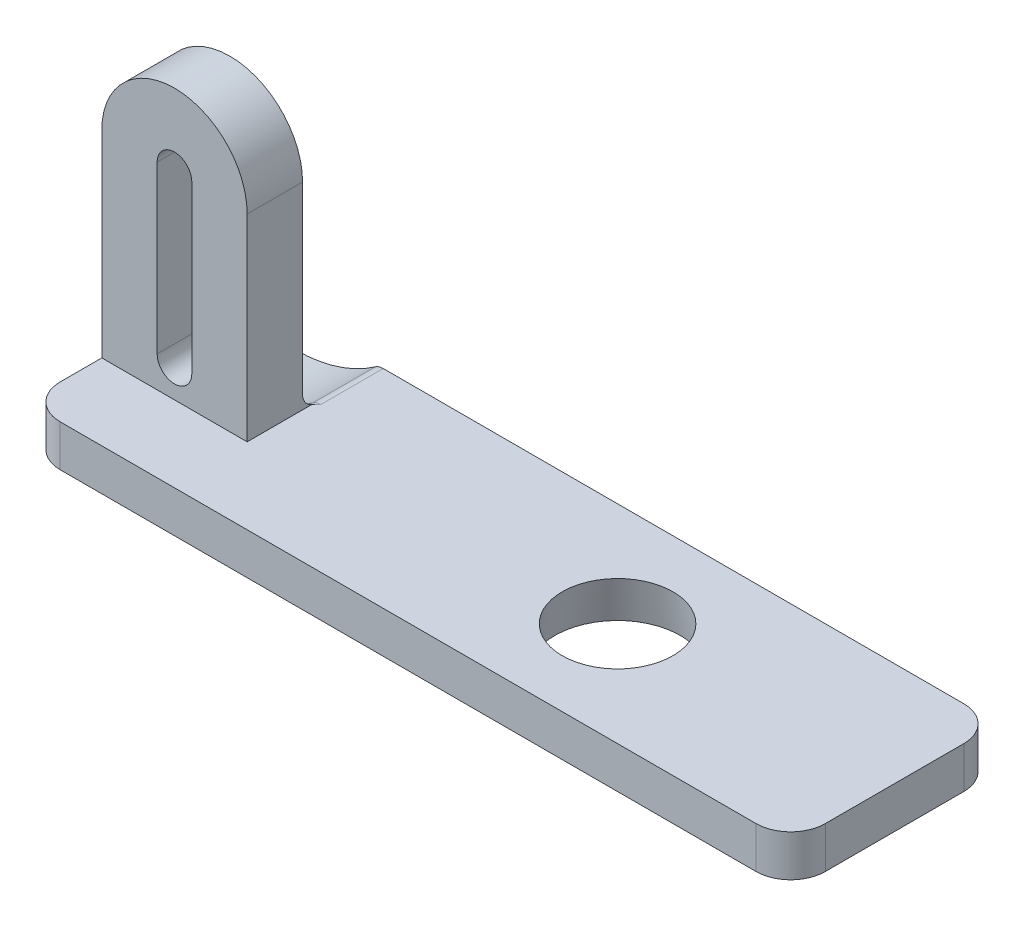
SolidWorks part; units mm, degrees
ref_plane "Front Plane" through (0, 0, 0) normal (0, 0, 1) x (1, 0, 0)
ref_plane "Top Plane" through (0, 0, 0) normal (0, 1, 0) x (1, 0, 0)
ref_plane "Right Plane" through (0, 0, 0) normal (1, 0, 0) x (0, 0, -1)
sketch "Sketch1" plane through (0, 0, 0) normal (0, 0, 1) x (1, 0, 0)
  line L0 (0, 12) -> (0, 0) construction
  line L1 (1.25, 12) -> (1.25, 0)
  line L2 (-1.25, 12) -> (-1.25, 0)
  line L3 (-5.25, 12) -> (-5.25, -5.25)
  line L4 (-5.25, -5.25) -> (50, -5.25)
  line L5 (5.25, 12) -> (5.25, -2.25)
  line L6 (5.25, -2.25) -> (50, -2.25)
  line L7 (50, -2.25) -> (50, -5.25)
  arc A0 (1.25, 12) -> (-1.25, 12) centre (0, 12) ccw
  arc A1 (-1.25, 0) -> (1.25, 0) centre (0, 0) ccw
  arc A2 (-5.25, 12) -> (5.25, 12) centre (0, 12) cw
  point P2 (0, 6)
  point P12 (0, -1.25)
  dimension "D3" = 4
  dimension "D1" = 12
  dimension "D2" = 2.5
  dimension "D4" = 4
  dimension "D5" = 50
  dimension "D6" = 3
extrude "Boss-Extrude1" add sketch "Sketch1" along normal mid plane 15
sketch "Sketch2" plane through (0, 0, 7.5) normal (0, 0, 1) x (1, 0, 0)
  line L0 (-5.25, 12) -> (-5.25, -5.25) construction
  line L1 (5.25, -2.25) -> (5.25, 12) construction
  line L2 (-5.25, 12) -> (-5.25, -2.25)
  line L3 (5.25, -2.25) -> (5.25, 12)
  line L4 (5.25, -2.25) -> (-5.25, -2.25)
  arc A0 (5.25, 12) -> (-5.25, 12) centre (0, 12) ccw construction
  arc A1 (5.25, 12) -> (-5.25, 12) centre (0, 12) ccw
extrude "Cut-Extrude1" cut sketch "Sketch2" against normal offset from surface (5.5 mm away) 2 up to plane "Front Plane"
extrude "Cut-Extrude2" cut sketch "Sketch2<2>" along normal offset from surface (5.5 mm away) 2 from surface up to plane "Front Plane" starting at face at (16.6667, 2.375, -7.5)
sketch "Sketch2<2>" plane through (0, 0, 7.5) normal (0, 0, 1) x (1, 0, 0) same geometry as "Sketch2"
sketch "Sketch3" plane through (0, -2.25, 0) normal (0, 1, 0) x (1, 0, 0)
  circle A0 centre (30, 0) radius 4
  dimension "D1" = 8
  dimension "D2" = 30
extrude "Cut-Extrude3" cut sketch "Sketch3" against normal through all draft 10 draft outward yes
fillet "Fillet1" radius 2.5 4 edges at (-5.25, -3.75, -7.5) (50, -3.75, -7.5) (50, -3.75, 7.5) (-5.25, -3.75, 7.5)
sketch "Sketch4" plane through (0, -2.25, 0) normal (0, 1, 0) x (1, 0, 0)
  line L0 (5.25, 2) -> (-5.25, 2) construction
  line L1 (5.25, 2) -> (-5.25, 2)
  line L2 (-5.25, 2) -> (-5.25, 5) construction
  line L3 (-5.25, 2) -> (-5.25, 5)
  line L4 (47.5, 7.5) -> (-2.75, 7.5) construction
  line L5 (5.25, 7.5) -> (-2.75, 7.5)
  line L6 (5.25, 2) -> (5.25, 7.5)
  arc A0 (-2.75, 7.5) -> (-5.25, 5) centre (-2.75, 5) ccw construction
  arc A1 (-2.75, 7.5) -> (-5.25, 5) centre (-2.75, 5) ccw
extrude "Cut-Extrude4" cut sketch "Sketch4" against normal blind 2
fillet "Fillet2" radius 10 1 edges at (5.25, -4.25, -4.75)
fillet "Fillet5" radius 1 1 edges at (5.25, -2.25, -4.75)
fillet "Fillet3" radius 1 3 edges at (2.2651, -3.7846, -2) (-3, -4.25, -2) (5.273, -2.2965, -2)
